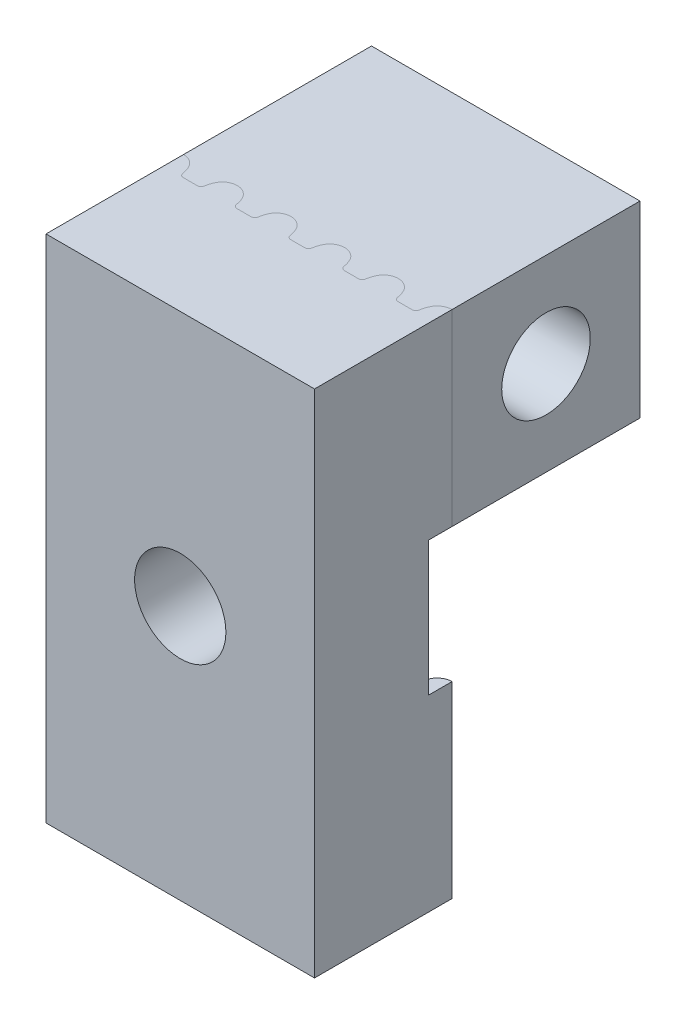
SolidWorks part; units mm, degrees
ref_plane "Front Plane" through (0, 0, 0) normal (0, 0, 1) x (1, 0, 0)
ref_plane "Top Plane" through (0, 0, 0) normal (0, 1, 0) x (1, 0, 0)
ref_plane "Right Plane" through (0, 0, 0) normal (1, 0, 0) x (0, 0, -1)
sketch "Sketch1" plane through (0, 0, 0) normal (0, 0, 1) x (1, 0, 0)
  line L1 (5, 9.5) -> (-5, 9.5)
  line L2 (5, 9.5) -> (5, -9.5)
  line L3 (5, -9.5) -> (-5, -9.5)
  line L4 (-5, 9.5) -> (-5, -9.5)
  line L5 (5, 9.5) -> (-5, -9.5) construction
  line L6 (5, -9.5) -> (-5, 9.5) construction
  point P0 (0, 0)
  dimension "D1" = 10
  dimension "D2" = 19
extrude "Boss-Extrude1" add sketch "Sketch1" along normal blind 4.25
hole_wizard "M3 Clearance Hole1" positions "Sketch3" profile "Sketch4" hole size "M3" standard "ANSI Metric" end condition through all
sketch "Sketch3" plane through (0, 0, 4.25) normal (0, 0, 1) x (1, 0, 0)
  point P0 (0, 0)
sketch "Sketch4" plane through (0, 0, 4.25) normal (1, 0, 0) x (0, -1, 0)
  line L0 (0, 0) -> (0, 4.25)
  line L1 (0, 4.25) -> (1.7, 4.25)
  line L2 (1.7, 4.25) -> (1.7, 0)
  line L5 (1.7, 0) -> (0, 0)
  line L11 (0, -6.35) -> (0, 107.95) construction
  dimension "Thru Hole Dia." = 3.4
  dimension "Thru Hole Depth" = 4.25
sketch "Sketch6" plane through (0, 9.5, 0) normal (0, 1, 0) x (1, 0, 0)
  line L0 (-5, 0) -> (-3, 0)
  line L1 (5, 0) -> (-5, 0) construction
  line L3 (-3.7421, 0.1225) -> (-4.2579, 0.1225)
  line L4 (-5, 0.1225) -> (-5, 0)
  line L5 (-5, 0.1225) -> (-5, 0.8725)
  line L6 (-4, 0) -> (-4, 0.5833) construction
  line L7 (-3, 0.1225) -> (-3, 0)
  line L8 (-3, 0.1225) -> (-3, 0.8725)
  arc A1 (-4.4065, 0.2522) -> (-4.5045, 0.5674) centre (-5.3973, 0.1171) ccw
  arc A2 (-4.5045, 0.5674) -> (-5, 0.8725) centre (-5, 0.3175) ccw
  arc A3 (-4.4065, 0.2522) -> (-4.2579, 0.1225) centre (-4.2579, 0.2725) ccw
  arc A4 (-3.5935, 0.2522) -> (-3.7421, 0.1225) centre (-3.7421, 0.2725) cw
  arc A5 (-3.5935, 0.2522) -> (-3.4955, 0.5674) centre (-2.6027, 0.1171) cw
  arc A6 (-3.4955, 0.5674) -> (-3, 0.8725) centre (-3, 0.3175) cw
  point P17 (-4, 0.1225)
  point P18 (-4, 0)
  dimension "D4" = 0.3
  dimension "D5" = 2
  dimension "D1" = 0.1225
  dimension "D2" = 1
  dimension "D3" = 0.75
  dimension "D6" = 0.1225
extrude "Boss-Extrude2" add sketch "Sketch6" against normal blind 7
pattern_linear "LPattern1" count 5 spacing 2 along (1, 0, 0) of "Boss-Extrude2"
mirror "Mirror1" about plane through (0, 0, 0) normal (0, 1, 0) of "LPattern1"
sketch "Sketch7" plane through (0, -9.5, 0) normal (0, -1, 0) x (1, 0, 0)
  line L5 (-5, -0.8725) -> (-5, -5.8725)
  line L6 (5, -0.8725) -> (5, -5.8725)
  line L7 (-5, -5.8725) -> (5, -5.8725)
  line L8 (-3.7421, -0.1225) -> (-4.2579, -0.1225) construction
  line L9 (-1.7421, -0.1225) -> (-2.2579, -0.1225) construction
  line L10 (0.2579, -0.1225) -> (-0.2579, -0.1225) construction
  line L11 (2.2579, -0.1225) -> (1.7421, -0.1225) construction
  line L12 (4.2579, -0.1225) -> (3.7421, -0.1225) construction
  line L13 (-3.7421, -0.1225) -> (-4.2579, -0.1225)
  line L14 (-1.7421, -0.1225) -> (-2.2579, -0.1225)
  line L15 (0.2579, -0.1225) -> (-0.2579, -0.1225)
  line L16 (2.2579, -0.1225) -> (1.7421, -0.1225)
  line L17 (4.2579, -0.1225) -> (3.7421, -0.1225)
  arc A26 (-5, -0.8725) -> (-4.5045, -0.5674) centre (-5, -0.3175) ccw construction
  arc A27 (-4.5045, -0.5674) -> (-4.4065, -0.2522) centre (-5.3973, -0.1171) ccw construction
  arc A28 (-4.2579, -0.1225) -> (-4.4065, -0.2522) centre (-4.2579, -0.2725) ccw construction
  arc A29 (-3.5935, -0.2522) -> (-3.7421, -0.1225) centre (-3.7421, -0.2725) ccw construction
  arc A30 (-3.5935, -0.2522) -> (-3.4955, -0.5674) centre (-2.6027, -0.1171) ccw construction
  arc A31 (-3.4955, -0.5674) -> (-2.5045, -0.5674) centre (-3, -0.3175) ccw construction
  arc A32 (-2.5045, -0.5674) -> (-2.4065, -0.2522) centre (-3.3973, -0.1171) ccw construction
  arc A33 (-2.2579, -0.1225) -> (-2.4065, -0.2522) centre (-2.2579, -0.2725) ccw construction
  arc A34 (-1.5935, -0.2522) -> (-1.7421, -0.1225) centre (-1.7421, -0.2725) ccw construction
  arc A35 (-1.5935, -0.2522) -> (-1.4955, -0.5674) centre (-0.6027, -0.1171) ccw construction
  arc A36 (-1.4955, -0.5674) -> (-0.5045, -0.5674) centre (-1, -0.3175) ccw construction
  arc A37 (-0.5045, -0.5674) -> (-0.4065, -0.2522) centre (-1.3973, -0.1171) ccw construction
  arc A38 (-0.2579, -0.1225) -> (-0.4065, -0.2522) centre (-0.2579, -0.2725) ccw construction
  arc A39 (0.4065, -0.2522) -> (0.2579, -0.1225) centre (0.2579, -0.2725) ccw construction
  arc A40 (0.4065, -0.2522) -> (0.5045, -0.5674) centre (1.3973, -0.1171) ccw construction
  arc A41 (0.5045, -0.5674) -> (1.4955, -0.5674) centre (1, -0.3175) ccw construction
  arc A42 (1.4955, -0.5674) -> (1.5935, -0.2522) centre (0.6027, -0.1171) ccw construction
  arc A43 (1.7421, -0.1225) -> (1.5935, -0.2522) centre (1.7421, -0.2725) ccw construction
  arc A44 (2.4065, -0.2522) -> (2.2579, -0.1225) centre (2.2579, -0.2725) ccw construction
  arc A45 (2.4065, -0.2522) -> (2.5045, -0.5674) centre (3.3973, -0.1171) ccw construction
  arc A46 (2.5045, -0.5674) -> (3.4955, -0.5674) centre (3, -0.3175) ccw construction
  arc A47 (3.4955, -0.5674) -> (3.5935, -0.2522) centre (2.6027, -0.1171) ccw construction
  arc A48 (3.7421, -0.1225) -> (3.5935, -0.2522) centre (3.7421, -0.2725) ccw construction
  arc A49 (4.4065, -0.2522) -> (4.2579, -0.1225) centre (4.2579, -0.2725) ccw construction
  arc A50 (4.4065, -0.2522) -> (4.5045, -0.5674) centre (5.3973, -0.1171) ccw construction
  arc A51 (4.5045, -0.5674) -> (5, -0.8725) centre (5, -0.3175) ccw construction
  arc A52 (-5, -0.8725) -> (-4.5045, -0.5674) centre (-5, -0.3175) ccw
  arc A53 (-4.5045, -0.5674) -> (-4.4065, -0.2522) centre (-5.3973, -0.1171) ccw
  arc A54 (-4.2579, -0.1225) -> (-4.4065, -0.2522) centre (-4.2579, -0.2725) ccw
  arc A55 (-3.5935, -0.2522) -> (-3.7421, -0.1225) centre (-3.7421, -0.2725) ccw
  arc A56 (-3.5935, -0.2522) -> (-3.4955, -0.5674) centre (-2.6027, -0.1171) ccw
  arc A57 (-3.4955, -0.5674) -> (-2.5045, -0.5674) centre (-3, -0.3175) ccw
  arc A58 (-2.5045, -0.5674) -> (-2.4065, -0.2522) centre (-3.3973, -0.1171) ccw
  arc A59 (-2.2579, -0.1225) -> (-2.4065, -0.2522) centre (-2.2579, -0.2725) ccw
  arc A60 (-1.5935, -0.2522) -> (-1.7421, -0.1225) centre (-1.7421, -0.2725) ccw
  arc A61 (-1.5935, -0.2522) -> (-1.4955, -0.5674) centre (-0.6027, -0.1171) ccw
  arc A62 (-1.4955, -0.5674) -> (-0.5045, -0.5674) centre (-1, -0.3175) ccw
  arc A63 (-0.5045, -0.5674) -> (-0.4065, -0.2522) centre (-1.3973, -0.1171) ccw
  arc A64 (-0.2579, -0.1225) -> (-0.4065, -0.2522) centre (-0.2579, -0.2725) ccw
  arc A65 (0.4065, -0.2522) -> (0.2579, -0.1225) centre (0.2579, -0.2725) ccw
  arc A66 (0.4065, -0.2522) -> (0.5045, -0.5674) centre (1.3973, -0.1171) ccw
  arc A67 (0.5045, -0.5674) -> (1.4955, -0.5674) centre (1, -0.3175) ccw
  arc A68 (1.4955, -0.5674) -> (1.5935, -0.2522) centre (0.6027, -0.1171) ccw
  arc A69 (1.7421, -0.1225) -> (1.5935, -0.2522) centre (1.7421, -0.2725) ccw
  arc A70 (2.4065, -0.2522) -> (2.2579, -0.1225) centre (2.2579, -0.2725) ccw
  arc A71 (2.4065, -0.2522) -> (2.5045, -0.5674) centre (3.3973, -0.1171) ccw
  arc A72 (2.5045, -0.5674) -> (3.4955, -0.5674) centre (3, -0.3175) ccw
  arc A73 (3.4955, -0.5674) -> (3.5935, -0.2522) centre (2.6027, -0.1171) ccw
  arc A74 (3.7421, -0.1225) -> (3.5935, -0.2522) centre (3.7421, -0.2725) ccw
  arc A75 (4.4065, -0.2522) -> (4.2579, -0.1225) centre (4.2579, -0.2725) ccw
  arc A76 (4.4065, -0.2522) -> (4.5045, -0.5674) centre (5.3973, -0.1171) ccw
  arc A77 (4.5045, -0.5674) -> (5, -0.8725) centre (5, -0.3175) ccw
  dimension "D1" = 5
extrude "Boss-Extrude4" add sketch "Sketch7" against normal up to surface (19 mm away) separate body up to face at (0, 9.5, -0.1114)
sketch "Sketch8" plane through (0, 0, -0.1225) normal (0, 0, 1) x (1, 0, 0)
  line L0 (-5, 9.5) -> (-5, -9.5) construction
  line L1 (5, 2.5) -> (-5, 2.5)
  line L2 (5, 2.5) -> (5, -2.5)
  line L3 (5, -2.5) -> (-5, -2.5)
  line L4 (-5, 2.5) -> (-5, -2.5)
  line L5 (5, 2.5) -> (-5, -2.5) construction
  line L6 (5, -2.5) -> (-5, 2.5) construction
  line L7 (-0.5045, 9.5) -> (-1.4955, 9.5) construction
  point P0 (0, 0)
  dimension "D1" = 7
extrude "Cut-Extrude1" cut sketch "Sketch8" against normal blind 0.75
hole_wizard "M3 Clearance Hole2" positions "Sketch10" profile "Sketch11" hole size "M3" standard "ANSI Metric" end condition through all
sketch "Sketch10" plane through (0, 0, -0.8725) normal (0, 0, 1) x (1, 0, 0)
  point P0 (0, 0)
sketch "Sketch11" plane through (0, 0, -0.8725) normal (1, 0, 0) x (0, -1, 0)
  line L0 (0, 0) -> (0, 5)
  line L1 (0, 5) -> (1.7, 5)
  line L2 (1.7, 5) -> (1.7, 0)
  line L5 (1.7, 0) -> (0, 0)
  line L11 (0, -6.35) -> (0, 107.95) construction
  dimension "Thru Hole Dia." = 3.4
  dimension "Thru Hole Depth" = 5
sketch "Sketch12" plane through (0, 0, -0.1225) normal (0, 0, 1) x (1, 0, 0)
  line L1 (-5, 2.5) -> (5, 2.5)
  line L2 (-5, 2.5) -> (-5, -9.5)
  line L3 (-5, -9.5) -> (5, -9.5)
  line L4 (5, 2.5) -> (5, -9.5)
  point P6 (0, 0)
extrude "Cut-Extrude2" cut sketch "Sketch12" against normal up to next (5.75 mm away)
sketch "Sketch13" plane through (0, 0, -5.8725) normal (0, 0, -1) x (-1, 0, 0)
  line L4 (-5, 2.5) -> (5, 2.5)
  line L5 (5, 2.5) -> (5, 9.5)
  line L6 (5, 9.5) -> (-5, 9.5)
  line L7 (-5, 9.5) -> (-5, 2.5)
  line L8 (-5, 2.5) -> (5, 2.5)
  line L9 (5, 2.5) -> (5, 9.5)
  line L10 (5, 9.5) -> (-5, 9.5)
  line L11 (-5, 9.5) -> (-5, 2.5)
  dimension "D1" = 0
extrude "Boss-Extrude5" add sketch "Sketch13" along normal blind 2
sketch "Sketch14" plane through (-5, 0, 0) normal (-1, 0, 0) x (0, 0, 1)
  line L0 (-4.3725, 9.5) -> (-4.3725, 2.5) construction
  line L1 (-7.8725, 9.5) -> (-0.8725, 9.5) construction
  line L2 (-7.8725, 2.5) -> (-0.8725, 2.5) construction
  line L3 (-7.8725, 6) -> (-0.8725, 6) construction
  line L4 (-7.8725, 2.5) -> (-7.8725, 9.5) construction
  line L5 (-0.8725, 9.5) -> (-0.8725, 2.5) construction
  circle A0 centre (-4.3725, 6) radius 2.35
  dimension "D1" = 4.7
extrude "Cut-Extrude3" cut sketch "Sketch14" against normal blind 3.8
sketch "Sketch15" plane through (-1.2, 0, 0) normal (-1, 0, 0) x (0, 0, 1)
  circle A0 centre (-4.3725, 6) radius 1.65
  dimension "D1" = 3.3
extrude "Cut-Extrude4" cut sketch "Sketch15" against normal through all
